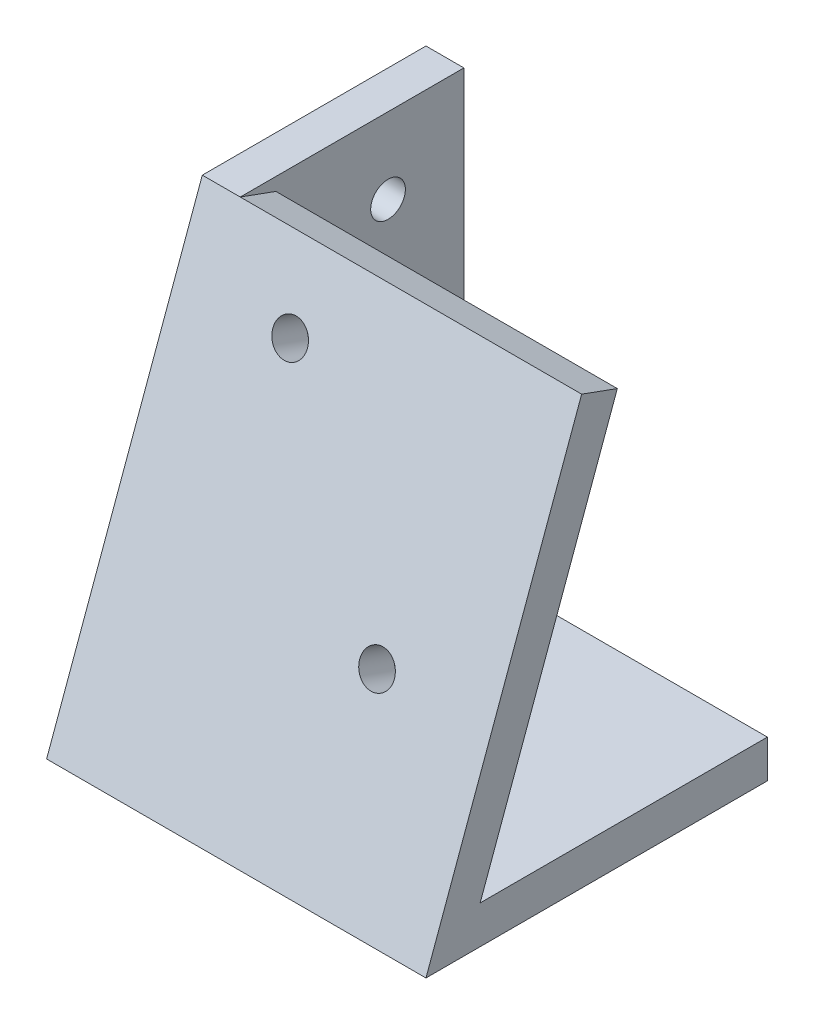
SolidWorks part; units mm, degrees
material "ABS"
ref_plane "Front Plane" through (0, 0, 0) normal (0, 0, 1) x (1, 0, 0)
ref_plane "Top Plane" through (0, 0, 0) normal (0, 1, 0) x (1, 0, 0)
ref_plane "Right Plane" through (0, 0, 0) normal (1, 0, 0) x (0, 0, -1)
sketch "Sketch1" plane through (0, 0, 0) normal (1, 0, 0) x (0, 0, -1)
  line L0 (0, 0) -> (-50, 0)
  line L1 (-50, 0) -> (-29.4788, 56.3816)
  line L2 (-29.4788, 56.3816) -> (-24.7803, 54.6715)
  line L3 (-24.7803, 54.6715) -> (-42.8593, 5)
  line L4 (-42.8593, 5) -> (0, 5)
  line L5 (0, 5) -> (0, 0)
  dimension "D1" = 60
  dimension "D2" = 50
  dimension "D3" = 70
  dimension "D4" = 5
  dimension "D5" = 5
extrude "Main" add sketch "Sketch1" along normal mid plane 50
sketch "Sketch2" plane through (0, 0, 0) normal (0, 0, -1) x (-1, 0, 0)
  line L0 (-25, 56.3816) -> (25, 56.3816) construction
  line L1 (-25, 0) -> (-20, 0)
  line L2 (-25, 0) -> (-25, 56.3816)
  line L3 (-25, 56.3816) -> (-20, 56.3816)
  line L4 (-20, 0) -> (-20, 56.3816)
  dimension "D1" = 5
extrude "Back" add sketch "Sketch2" against normal up to next
hole_wizard "Base Holes" positions "3DSketch4" profile "Sketch5" hole size "#8" standard "ANSI Inch"
sketch3d "3DSketch4"
  line L0 (-25, 5, 0) -> (-25, 5, 42.8593) construction
  line L4 (20, 5, 42.8593) -> (-25, 5, 42.8593) construction
  point P0 (10, 5, 32.6993)
  point P2 (-10, 5, 32.6993)
  dimension "D1" = 15
  dimension "D2" = 15
  dimension "D3" = 10.16
  dimension "D4" = 10.16
sketch "Sketch5" plane through (10, 5, 32.6993) normal (1, 0, 0) x (0, 0, 1)
  line L0 (0, 0) -> (0, 5)
  line L1 (0, 5) -> (2.286, 5)
  line L2 (2.286, 5) -> (2.286, 0)
  line L5 (2.286, 0) -> (0, 0)
  line L10 (0, 5) -> (-2.286, 5) construction
  line L11 (0, -6.35) -> (0, 107.95) construction
  dimension "Hole Dia." = 4.572
  dimension "Hole Depth" = 5
  dimension "Drill Angle" = 180
hole_wizard "BackPanelHoles" positions "Sketch6" profile "Sketch7" hole size "#8" standard "ANSI Inch"
sketch "Sketch6" plane through (20, 0, 0) normal (-1, 0, 0) x (0, 0, 1)
  line L0 (29.4788, 56.3816) -> (0, 56.3816) construction
  line L1 (0, 5) -> (0, 56.3816) construction
  line L2 (50, 0) -> (0, 0) construction
  point P0 (10, 46.3816)
  point P2 (25, 20)
  dimension "D1" = 10
  dimension "D2" = 10
  dimension "D3" = 20
  dimension "D4" = 25
sketch "Sketch7" plane through (20, 46.3816, 10) normal (0, 1, 0) x (0, 0, 1)
  line L0 (0, 0) -> (0, 5)
  line L1 (0, 5) -> (2.286, 5)
  line L2 (2.286, 5) -> (2.286, 0)
  line L5 (2.286, 0) -> (0, 0)
  line L10 (0, 5) -> (-2.286, 5) construction
  line L11 (0, -6.35) -> (0, 107.95) construction
  dimension "Hole Dia." = 4.572
  dimension "Hole Depth" = 5
  dimension "Drill Angle" = 180
hole_wizard "#8 (0.18) Diameter Hole3" positions "3DSketch5" profile "Sketch8" hole size "#8" standard "ANSI Inch"
sketch3d "3DSketch5"
  line L1 (20, 56.3816, 29.4788) -> (-25, 56.3816, 29.4788) construction
  line L2 (25, 0, 50) -> (-25, 0, 50) construction
  line L3 (-25, 56.3816, 29.4788) -> (-25, 0, 50) construction
  line L4 (25, 56.3816, 29.4788) -> (25, 0, 50) construction
  point P0 (-10, 46.9846, 32.899)
  point P2 (10, 23.4923, 41.4495)
  dimension "D1" = 15
  dimension "D2" = 10
  dimension "D3" = 25
  dimension "D4" = 15
sketch "Sketch8" plane through (-10, 46.9846, 32.899) normal (1, 0, 0) x (0, -0.9397, 0.342)
  line L0 (0, 0) -> (0, 5)
  line L1 (0, 5) -> (2.286, 5)
  line L2 (2.286, 5) -> (2.286, 0)
  line L5 (2.286, 0) -> (0, 0)
  line L10 (0, 5) -> (-2.286, 5) construction
  line L11 (0, -6.35) -> (0, 107.95) construction
  dimension "Hole Dia." = 4.572
  dimension "Hole Depth" = 5
  dimension "Drill Angle" = 180
ref_plane "Midplane" through (0, 0, 0) normal (-1, 0, 0) x (0, 0, 1)
mirror "Mirror1" about plane through (0, 0, 0) normal (-1, 0, 0) of "BackPanelHoles", "Back"
sketch "Sketch9" plane through (20, 0, 0) normal (-1, 0, 0) x (0, 0, 1)
  line L0 (29.4788, 56.3816) -> (0, 56.3816)
  line L1 (0, 56.3816) -> (0, 5)
  line L2 (0, 5) -> (42.8593, 5)
  line L3 (42.8593, 5) -> (24.7803, 54.6715)
  line L4 (24.7803, 54.6715) -> (29.4788, 56.3816)
extrude "Mirror Cut" cut sketch "Sketch9" against normal up to next
sketch "Sketch10" plane through (0, 5, 0) normal (0, 1, 0) x (1, 0, 0)
  line L0 (25, -42.8593) -> (25, 0) construction
  line L1 (-20, 0) -> (25, 0)
  line L2 (-20, 0) -> (-20, -5)
  line L3 (-20, -5) -> (25, -5)
  line L4 (25, 0) -> (25, -5)
  dimension "D1" = 5
extrude "BatteryCut" cut sketch "Sketch10" against normal up to next
